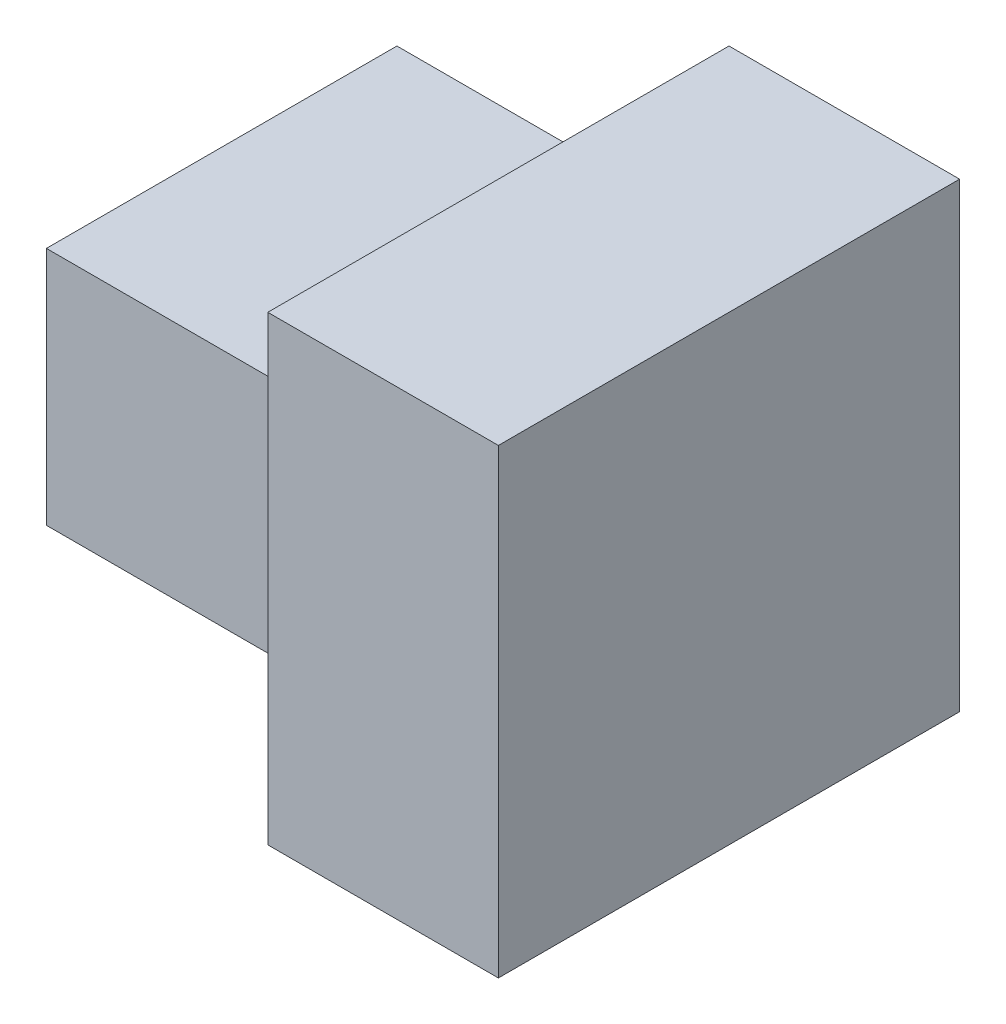
SolidWorks part; units mm, degrees
ref_plane "Front Plane" through (0, 0, 0) normal (0, 0, 1) x (1, 0, 0)
ref_plane "Top Plane" through (0, 0, 0) normal (0, 1, 0) x (1, 0, 0)
ref_plane "Right Plane" through (0, 0, 0) normal (1, 0, 0) x (0, 0, -1)
sketch "Sketch1" plane through (0, 0, 0) normal (1, 0, 0) x (0, 0, -1)
  line L0 (-2.2, 1) -> (2.2, 1)
  line L1 (-2.5, 0.7) -> (-2.5, -0.7)
  line L2 (-2.2, -1) -> (2.2, -1)
  line L3 (2.5, -0.7) -> (2.5, 0.7)
  arc A0 (-2.5, -0.7) -> (-2.2, -1) centre (-2.2, -0.7) ccw
  arc A1 (2.2, -1) -> (2.5, -0.7) centre (2.2, -0.7) ccw
  arc A2 (2.5, 0.7) -> (2.2, 1) centre (2.2, 0.7) ccw
  arc A3 (-2.2, 1) -> (-2.5, 0.7) centre (-2.2, 0.7) ccw
  point P7 (-2.5, -1)
  point P12 (2.5, 1)
  point P15 (-2.5, 1)
  dimension "D5" = 0.3
  dimension "D1" = 5
  dimension "D2" = 2.5
  dimension "D3" = 2
  dimension "D4" = 1
extrude "Boss-Extrude1" add sketch "Sketch1" along normal blind 5
sketch "Sketch2" plane through (0, 0, 0) normal (-1, 0, 0) x (0, 0, 1)
  line L0 (3.5, 2.8) -> (-3.5, 2.8)
  line L1 (2.5, 0.7) -> (2.5, -0.7) construction
  line L2 (-2.2, 1) -> (2.2, 1) construction
  line L3 (3.5, 2.8) -> (3.5, -1.8)
  line L4 (-2.5, -0.7) -> (-2.5, 0.7) construction
  line L5 (-3.5, 2.8) -> (-3.5, -1.8)
  line L6 (-2.5, -2.8) -> (2.5, -2.8)
  line L7 (2.2, -1) -> (-2.2, -1) construction
  line L8 (3.5, -1.8) -> (2.5, -2.8)
  line L9 (-3.5, -1.8) -> (-2.5, -2.8)
  line L10 (3.8, -2.1) -> (2.8, -3.1)
  line L11 (3.8, 3.1) -> (-3.8, 3.1)
  line L12 (3.8, 3.1) -> (3.8, -2.1)
  line L13 (2.8, -3.1) -> (-2.8, -3.1)
  line L14 (-3.8, 3.1) -> (-3.8, -2.1)
  line L15 (-2.8, -3.1) -> (-3.8, -2.1)
  point P2 (2.5, 0)
  point P8 (3.5, -2.8)
  point P12 (-3.5, -2.8)
  point P18 (-3.8, -3.1)
  point P19 (3.8, -3.1)
  dimension "D1" = 1
  dimension "D2" = 1.8
  dimension "D3" = 1
  dimension "D4" = 1.8
  dimension "D5" = 0.3
  dimension "D6" = 0.3
  dimension "D9" = 0.3
  dimension "D10" = 0.3
extrude "Boss-Extrude2" add sketch "Sketch2" against normal up to vertex (5 mm away) separate body up to point (5, 1, -2.2)
chamfer "Chamfer1" distance 0.3 angle 45 8 edges at (0, 1, 0) (0, -1, 0) (0, -0.9121, -2.4121) (0, -0.9121, 2.4121) (0, 0, -2.5) (0, 0, 2.5) (0, 0.9121, -2.4121) (0, 0.9121, 2.4121)
chamfer "Chamfer2" distance 0.2 angle 45 6 edges at (0, -2.3, -3) (0, -2.8, 0) (0, -2.3, 3) (0, 0.5, 3.5) (0, 2.8, 0) (0, 0.5, -3.5)
sketch "Sketch3" plane through (5, 0, 0) normal (1, 0, 0) x (0, 0, -1)
  line L0 (-3.8, -2.1) -> (-2.8, -3.1)
  line L1 (-3.8, 3.1) -> (3.8, 3.1)
  line L2 (-3.8, 3.1) -> (-3.8, -2.1)
  line L3 (-2.8, -3.1) -> (2.8, -3.1)
  line L4 (3.8, 3.1) -> (3.8, -2.1)
  line L5 (2.8, -3.1) -> (3.8, -2.1)
extrude "Boss-Extrude3" add sketch "Sketch3" along normal blind 1
sketch "Sketch4" plane through (0, -3.1, 0) normal (0, -1, 0) x (1, 0, 0)
  line L0 (1, 0.8) -> (1, -0.8)
  line L1 (6, -2.8) -> (0, -2.8) construction
  line L2 (2.0552, -0.8) -> (2.0552, 0.8)
  line L3 (6, 2.8) -> (0, 2.8) construction
  line L6 (0, -2.8) -> (0, 2.8) construction
  arc A0 (1, 0.8) -> (2.0552, 0.8) centre (1.5276, 0.8) cw
  arc A1 (1, -0.8) -> (2.0552, -0.8) centre (1.5276, -0.8) ccw
  dimension "D1" = 2
  dimension "D2" = 2
  dimension "D3" = 1
extrude "Boss-Extrude4" add sketch "Sketch4" against normal blind 0.6
chamfer "Chamfer4" distance 0.2 angle 45 4 edges at (2.0552, -2.5, 0) (1.5276, -2.5, 1.3276) (1.5276, -2.5, -1.3276) (1, -2.5, 0)
sketch "Sketch5" plane through (6, 0, 0) normal (1, 0, 0) x (0, 0, -1)
  line L0 (-3.8, 3.1) -> (-3.8, -2.1) construction
  line L1 (-5, 5.5) -> (5, 5.5)
  line L2 (-5, 5.5) -> (-5, -4.5)
  line L3 (-5, -4.5) -> (5, -4.5)
  line L4 (5, 5.5) -> (5, -4.5)
  line L7 (3.8, 3.1) -> (-3.8, 3.1) construction
  point P7 (-3.8, 0.5)
  point P8 (0, 3.1)
  point P10 (-3.8, 0.5)
  point P13 (0, 3.1)
  dimension "D1" = 5
  dimension "D2" = 5
  dimension "D3" = 5
  dimension "D4" = 5
extrude "Boss-Extrude5" add sketch "Sketch5" along normal blind 5
fillet "Fillet1" radius 0.5 6 edges at (6, -2.6, -3.3) (6, -3.1, 0) (6, -2.6, 3.3) (6, 0.5, 3.8) (6, 3.1, 0) (6, 0.5, -3.8)
